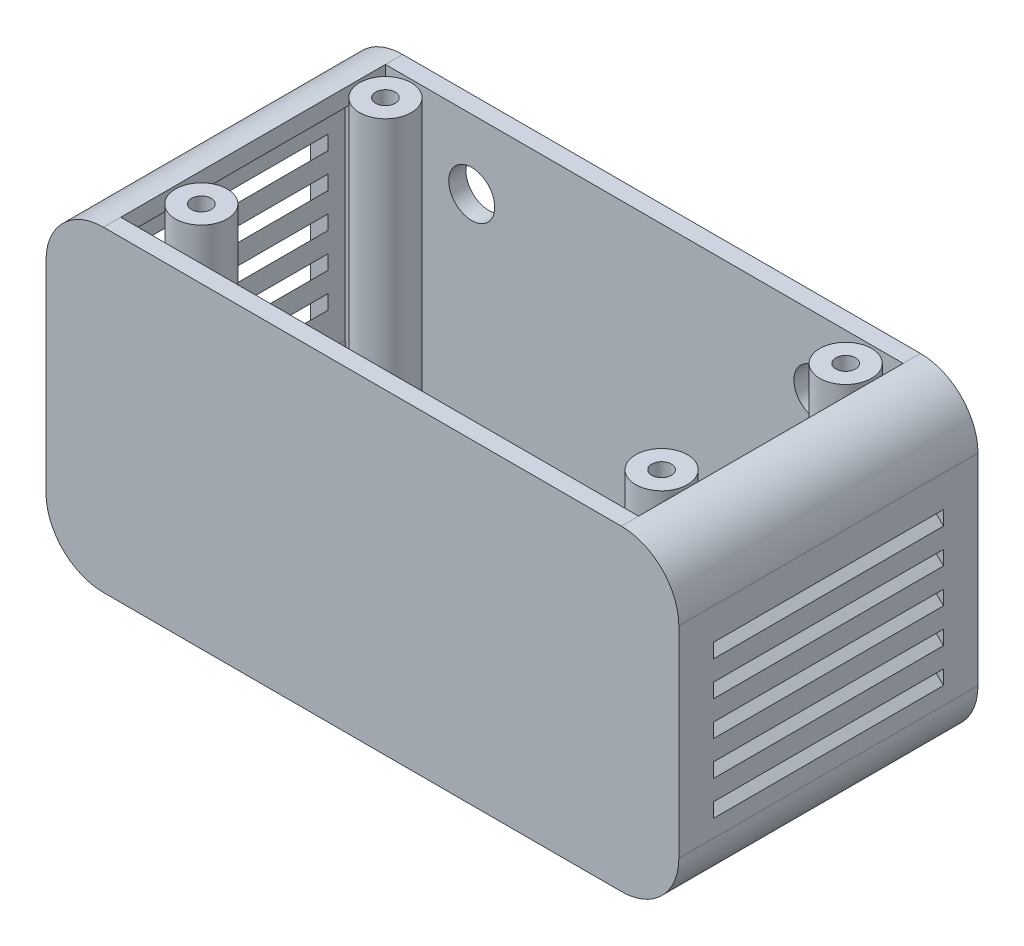
SolidWorks part; units mm, degrees
material "ABS"
ref_plane "Front Plane" through (0, 0, 0) normal (0, 0, 1) x (1, 0, 0)
ref_plane "Top Plane" through (0, 0, 0) normal (0, 1, 0) x (1, 0, 0)
ref_plane "Right Plane" through (0, 0, 0) normal (1, 0, 0) x (0, 0, -1)
sketch "Sketch1" plane through (0, 0, 0) normal (0, 0, 1) x (1, 0, 0)
  line L0 (-45, -55) -> (45, -55)
  line L1 (55, -45) -> (55, -10)
  line L2 (45, 0) -> (-45, 0)
  line L3 (-55, -10) -> (-55, -45)
  arc A0 (45, -55) -> (55, -45) centre (45, -45) ccw
  arc A1 (55, -10) -> (45, 0) centre (45, -10) ccw
  arc A2 (-45, 0) -> (-55, -10) centre (-45, -10) ccw
  arc A3 (-55, -45) -> (-45, -55) centre (-45, -45) ccw
extrude "Boss-Extrude1" add sketch "Sketch1" along normal blind 52
shell "Shell1" thickness 3 removed face at (0, 0, 26)
sketch "Sketch2" plane through (0, 0, 0) normal (0, 1, 0) x (1, 0, 0)
  circle A0 centre (-40, -8) radius 4.5
  circle A1 centre (40, -8) radius 4.5
  circle A2 centre (-40, -40) radius 4.5
  circle A3 centre (40, -40) radius 4.5
extrude "Boss-Extrude2" add sketch "Sketch2" against normal blind 52
sketch "Sketch3" plane through (0, -55, 0) normal (0, -1, 0) x (1, 0, 0)
  circle A0 centre (-40, 8) radius 3.25
  circle A1 centre (40, 8) radius 3.25
  circle A2 centre (-40, 40) radius 3.25
  circle A3 centre (40, 40) radius 3.25
extrude "Cut-Extrude1" cut sketch "Sketch3" against normal blind 49
sketch "Sketch4" plane through (0, -6, 0) normal (0, -1, 0) x (1, 0, 0)
  circle A0 centre (-40, 8) radius 1.7
  circle A1 centre (40, 8) radius 1.7
  circle A2 centre (-40, 40) radius 1.7
  circle A3 centre (40, 40) radius 1.7
extrude "Cut-Extrude2" cut sketch "Sketch4" against normal through all
ref_plane "Plane1" through (0, 0, 26) normal (0, 0, 1) x (1, 0, 0)
sketch "Sketch5" plane through (0, 0, 26) normal (0, 0, 1) x (1, 0, 0)
  line L0 (-51, -14) -> (-51, -11.5)
  line L1 (-51, -11.5) -> (-55.5, -16)
  line L2 (-55.5, -16) -> (-55.5, -18.5)
  line L3 (-55.5, -18.5) -> (-51, -14)
  line L4 (51, -14) -> (51, -11.5)
  line L5 (51, -11.5) -> (55.5, -16)
  line L6 (55.5, -16) -> (55.5, -18.5)
  line L7 (55.5, -18.5) -> (51, -14)
  line L8 (-51, -20) -> (-51, -17.5)
  line L9 (-51, -17.5) -> (-55.5, -22)
  line L10 (-55.5, -22) -> (-55.5, -24.5)
  line L11 (-55.5, -24.5) -> (-51, -20)
  line L12 (51, -20) -> (51, -17.5)
  line L13 (51, -17.5) -> (55.5, -22)
  line L14 (55.5, -22) -> (55.5, -24.5)
  line L15 (55.5, -24.5) -> (51, -20)
  line L16 (-51, -26) -> (-51, -23.5)
  line L17 (-51, -23.5) -> (-55.5, -28)
  line L18 (-55.5, -28) -> (-55.5, -30.5)
  line L19 (-55.5, -30.5) -> (-51, -26)
  line L20 (51, -26) -> (51, -23.5)
  line L21 (51, -23.5) -> (55.5, -28)
  line L22 (55.5, -28) -> (55.5, -30.5)
  line L23 (55.5, -30.5) -> (51, -26)
  line L24 (-51, -32) -> (-51, -29.5)
  line L25 (-51, -29.5) -> (-55.5, -34)
  line L26 (-55.5, -34) -> (-55.5, -36.5)
  line L27 (-55.5, -36.5) -> (-51, -32)
  line L28 (51, -32) -> (51, -29.5)
  line L29 (51, -29.5) -> (55.5, -34)
  line L30 (55.5, -34) -> (55.5, -36.5)
  line L31 (55.5, -36.5) -> (51, -32)
  line L32 (-51, -38) -> (-51, -35.5)
  line L33 (-51, -35.5) -> (-55.5, -40)
  line L34 (-55.5, -40) -> (-55.5, -42.5)
  line L35 (-55.5, -42.5) -> (-51, -38)
  line L36 (51, -38) -> (51, -35.5)
  line L37 (51, -35.5) -> (55.5, -40)
  line L38 (55.5, -40) -> (55.5, -42.5)
  line L39 (55.5, -42.5) -> (51, -38)
extrude "Cut-Extrude3" cut sketch "Sketch5" against normal blind 20 and the other way blind 20
sketch "Sketch6" plane through (0, -55, 0) normal (0, -1, 0) x (1, 0, 0)
  line L0 (-33, 12) -> (-33, 40) construction
  line L1 (-34.5, 12) -> (-34.5, 40)
  line L2 (-31.5, 12) -> (-31.5, 40)
  line L3 (-27, 12) -> (-27, 40) construction
  line L4 (-28.5, 12) -> (-28.5, 40)
  line L5 (-25.5, 12) -> (-25.5, 40)
  line L6 (-21, 12) -> (-21, 40) construction
  line L7 (-22.5, 12) -> (-22.5, 40)
  line L8 (-19.5, 12) -> (-19.5, 40)
  line L9 (-15, 12) -> (-15, 40) construction
  line L10 (-16.5, 12) -> (-16.5, 40)
  line L11 (-13.5, 12) -> (-13.5, 40)
  line L12 (-9, 12) -> (-9, 40) construction
  line L13 (-10.5, 12) -> (-10.5, 40)
  line L14 (-7.5, 12) -> (-7.5, 40)
  line L15 (-3, 12) -> (-3, 40) construction
  line L16 (-4.5, 12) -> (-4.5, 40)
  line L17 (-1.5, 12) -> (-1.5, 40)
  line L18 (33, 12) -> (33, 40) construction
  line L19 (31.5, 12) -> (31.5, 40)
  line L20 (34.5, 12) -> (34.5, 40)
  arc A0 (-34.5, 12) -> (-31.5, 12) centre (-33, 12) ccw
  arc A1 (-31.5, 40) -> (-34.5, 40) centre (-33, 40) ccw
  arc A2 (-28.5, 12) -> (-25.5, 12) centre (-27, 12) ccw
  arc A3 (-25.5, 40) -> (-28.5, 40) centre (-27, 40) ccw
  arc A4 (-22.5, 12) -> (-19.5, 12) centre (-21, 12) ccw
  arc A5 (-19.5, 40) -> (-22.5, 40) centre (-21, 40) ccw
  arc A6 (-16.5, 12) -> (-13.5, 12) centre (-15, 12) ccw
  arc A7 (-13.5, 40) -> (-16.5, 40) centre (-15, 40) ccw
  arc A8 (-10.5, 12) -> (-7.5, 12) centre (-9, 12) ccw
  arc A9 (-7.5, 40) -> (-10.5, 40) centre (-9, 40) ccw
  arc A10 (-4.5, 12) -> (-1.5, 12) centre (-3, 12) ccw
  arc A11 (-1.5, 40) -> (-4.5, 40) centre (-3, 40) ccw
  arc A12 (31.5, 12) -> (34.5, 12) centre (33, 12) ccw
  arc A13 (34.5, 40) -> (31.5, 40) centre (33, 40) ccw
  point P2 (-33, 26)
  point P7 (-27, 26)
  point P14 (-21, 26)
  point P21 (-15, 26)
  point P28 (-9, 26)
  point P35 (-3, 26)
  point P42 (33, 26)
  point P49 (0, 0)
extrude "Cut-Extrude4" cut sketch "Sketch6" against normal blind 3.5
sketch "Sketch7" plane through (0, 0, 0) normal (0, 0, -1) x (-1, 0, 0)
  circle A0 centre (30, -12) radius 4
  circle A1 centre (-30, -12) radius 4
extrude "Cut-Extrude5" cut sketch "Sketch7" against normal blind 3.5
sketch "Sketch8" plane through (0, -52, 0) normal (0, 1, 0) x (1, 0, 0)
  line L0 (-30.25, -26) -> (30.25, -26) construction
  line L1 (-47, -36) -> (-41, -36)
  line L2 (-47, -36) -> (-47, -16)
  line L3 (-47, -16) -> (-41, -16)
  line L4 (-41, -36) -> (-41, -16)
  line L5 (-47, -36) -> (-41, -16) construction
  line L6 (-47, -16) -> (-41, -36) construction
  point P0 (-44, -26)
extrude "Boss-Extrude3" add sketch "Sketch8" along normal blind 8
sketch "Sketch9" plane through (0, -44, 0) normal (0, 1, 0) x (1, 0, 0)
  line L0 (-30.25, -26) -> (30.25, -26) construction
  line L1 (-44.95, -34.3) -> (-43.05, -34.3)
  line L2 (-44.95, -34.3) -> (-44.95, -17.7)
  line L3 (-44.95, -17.7) -> (-43.05, -17.7)
  line L4 (-43.05, -34.3) -> (-43.05, -17.7)
  line L5 (-44.95, -34.3) -> (-43.05, -17.7) construction
  line L6 (-44.95, -17.7) -> (-43.05, -34.3) construction
  point P0 (-44, -26)
extrude "Cut-Extrude6" cut sketch "Sketch9" against normal blind 6
sketch "Sketch10" plane through (0, -52, 0) normal (0, 1, 0) x (1, 0, 0)
  circle A0 centre (15, -26) radius 15
  circle A1 centre (15, -26) radius 9.1
extrude "Boss-Extrude4" add sketch "Sketch10" along normal blind 8
sketch "Sketch11" plane through (0, -55, 0) normal (0, -1, 0) x (1, 0, 0)
  circle A0 centre (15, 26) radius 9.1
extrude "Cut-Extrude7" cut sketch "Sketch11" against normal blind 3.5
